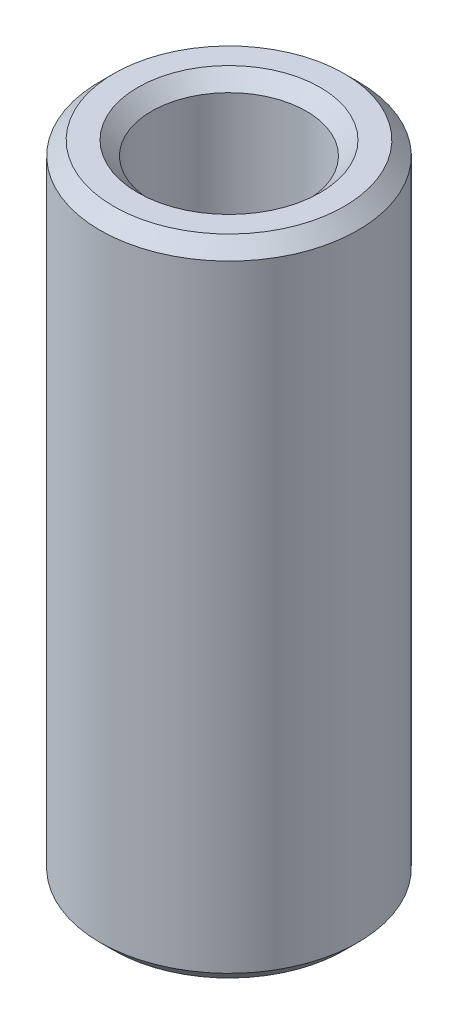
SolidWorks part; units mm, degrees
ref_plane "Front Plane" through (0, 0, 0) normal (0, 0, 1) x (1, 0, 0)
ref_plane "Top Plane" through (0, 0, 0) normal (0, 1, 0) x (1, 0, 0)
ref_plane "Right Plane" through (0, 0, 0) normal (1, 0, 0) x (0, 0, -1)
sketch "Sketch1" plane through (0, 0, 0) normal (0, 1, 0) x (1, 0, 0)
  circle A0 centre (0, 0) radius 7.5
  dimension "SLEEVE_OD" = 15
extrude "Boss-Extrude1" add sketch "Sketch1" along normal blind 37.4839
sketch "Sketch2" plane through (0, 0, 0) normal (0, 1, 0) x (1, 0, 0)
  circle A0 centre (0, 0) radius 4.5063
  dimension "BORE_D" = 9.0127
extrude "Cut-Extrude1" cut sketch "Sketch2" along normal through all
chamfer "Chamfer1" distance 0.8004 angle 45 4 edges at (0, 37.4839, 4.5063) (0, 0, 4.5063) (0, 0, 7.5) (0, 37.4839, 7.5)
